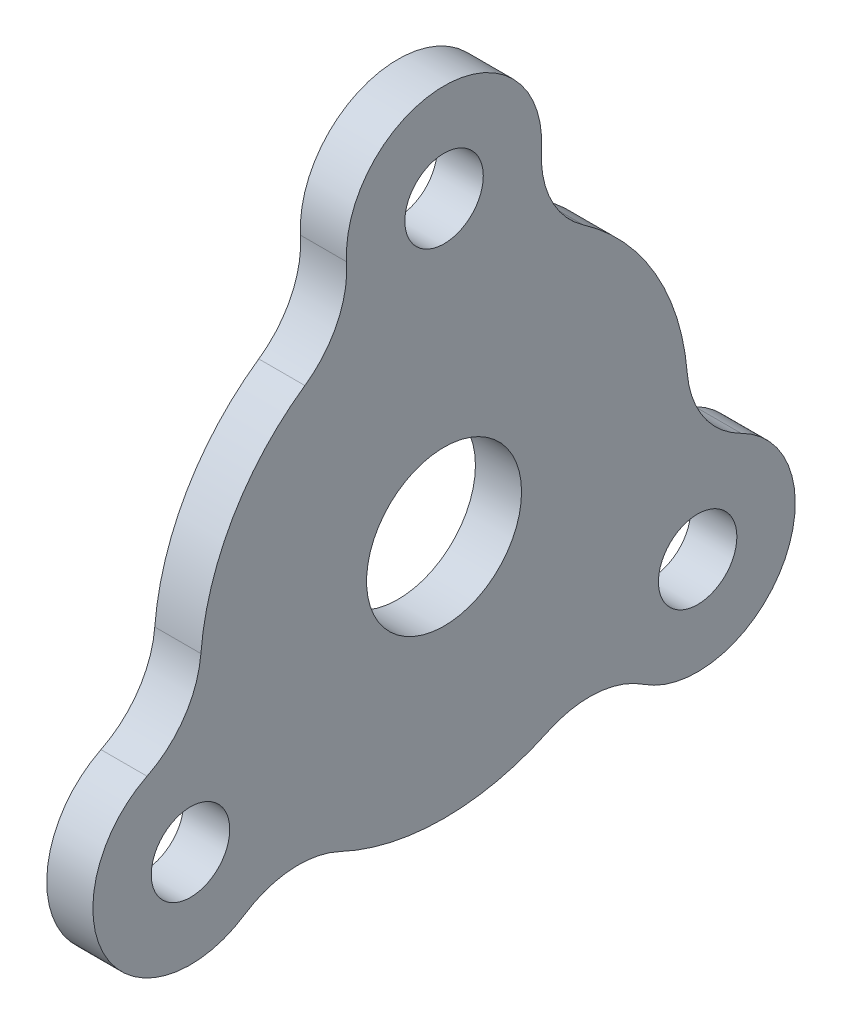
SolidWorks part; units mm, degrees
material "AR500"
ref_plane "Front Plane" through (0, 0, 0) normal (0, 0, 1) x (1, 0, 0)
ref_plane "Top Plane" through (0, 0, 0) normal (0, 1, 0) x (1, 0, 0)
ref_plane "Right Plane" through (0, 0, 0) normal (1, 0, 0) x (0, 0, -1)
sketch "Sketch1" plane through (0, 0, 0) normal (1, 0, 0) x (0, 0, -1)
  line L1 (0, 19.05) -> (-16.4978, -9.525) construction
  line L2 (-16.4978, -9.525) -> (16.4978, -9.525) construction
  line L3 (16.4978, -9.525) -> (0, 19.05) construction
  arc A1 (-9.0537, 13.0402) -> (-15.82, 1.3206) centre (0, 0) ccw
  circle A2 centre (0, 19.05) radius 2.5527
  circle A3 centre (-16.4978, -9.525) radius 2.5527
  circle A4 centre (16.4978, -9.525) radius 2.5527
  arc A6 (-15.82, 1.3206) -> (-19.3229, -3.8381) centre (-22.148, 1.8489) cw
  arc A7 (-19.3229, -3.8381) -> (-12.9853, -14.8151) centre (-16.4978, -9.525) ccw
  arc A8 (-12.9853, -14.8151) -> (-6.7663, -14.3608) centre (-9.4728, -20.1051) cw
  circle A9 centre (0, 0) radius 19.05 construction
  arc A10 (9.0537, 13.0402) -> (6.3376, 18.6531) centre (12.6752, 18.2563) cw
  arc A11 (6.3376, 18.6531) -> (-6.3376, 18.6531) centre (0, 19.05) ccw
  arc A12 (-6.3376, 18.6531) -> (-9.0537, 13.0402) centre (-12.6752, 18.2563) cw
  arc A13 (6.7663, -14.3608) -> (12.9853, -14.8151) centre (9.4728, -20.1051) cw
  arc A14 (12.9853, -14.8151) -> (19.3229, -3.8381) centre (16.4978, -9.525) ccw
  arc A15 (19.3229, -3.8381) -> (15.82, 1.3206) centre (22.148, 1.8489) cw
  circle A16 centre (0, 19.05) radius 2.0193 construction
  arc A17 (15.82, 1.3206) -> (9.0537, 13.0402) centre (0, 0) ccw
  arc A19 (-6.7663, -14.3608) -> (6.7663, -14.3608) centre (0, 0) ccw
  point P35 (0, 0)
  dimension "D4" = 5.1054
  dimension "D5" = 6.35
  dimension "D6" = 6.35
  dimension "D7" = 15.875
  dimension "D2" = 3
extrude "Boss-Extrude1" add sketch "Sketch1" along normal blind 3
hole_wizard "3/8 Clearance Hole1" positions "Sketch5" profile "Sketch6" hole size "3/8" standard "ANSI Inch" end condition through all
sketch "Sketch5" plane through (3, 0, 0) normal (1, 0, 0) x (0, 0, -1)
  point P0 (0, 0)
sketch "Sketch6" plane through (3, 0, 0) normal (0, 1, 0) x (0, 0, -1)
  line L0 (0, 0) -> (0, 3)
  line L1 (0, 3) -> (5.0419, 3)
  line L2 (5.0419, 3) -> (5.0419, 0)
  line L5 (5.0419, 0) -> (0, 0)
  line L11 (0, -6.35) -> (0, 107.95) construction
  dimension "Thru Hole Dia." = 10.0838
  dimension "Thru Hole Depth" = 3
